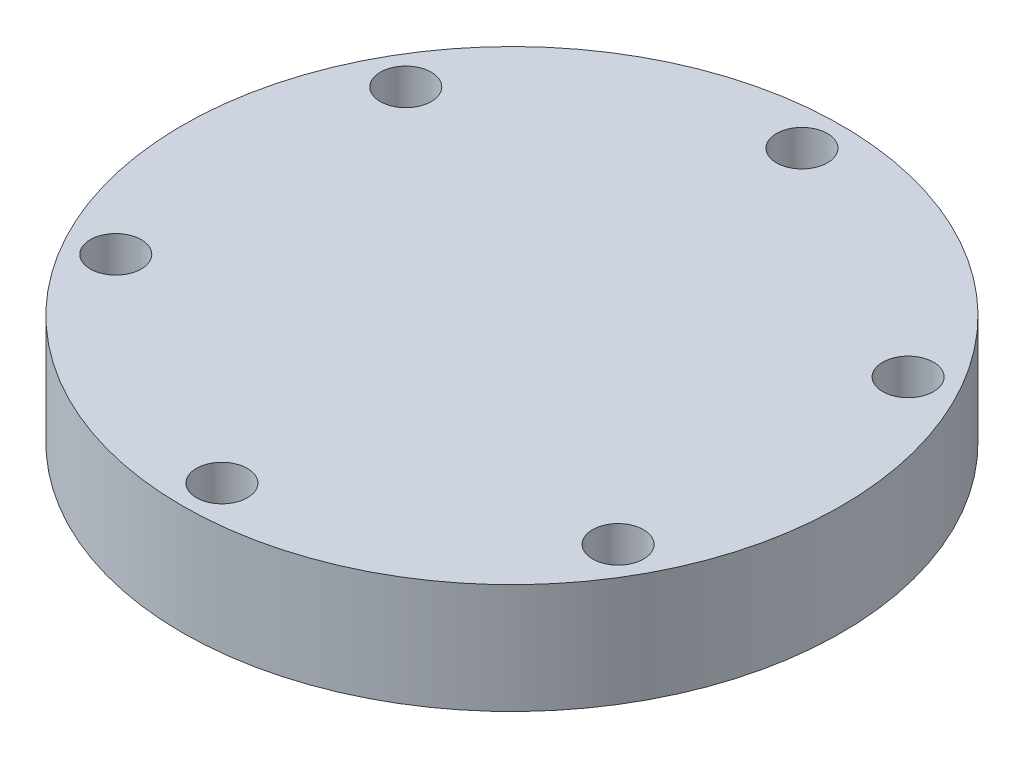
SolidWorks part; units mm, degrees
material "Copper"
ref_plane "Front Plane" through (0, 0, 0) normal (0, 0, 1) x (1, 0, 0)
ref_plane "Top Plane" through (0, 0, 0) normal (0, 1, 0) x (1, 0, 0)
ref_plane "Right Plane" through (0, 0, 0) normal (1, 0, 0) x (0, 0, -1)
ref_axis "Y Axis" through (0, 6.6675, 0) along (0, -1, 0)
sketch "outer" plane through (0, 0, 0) normal (0, 1, 0) x (1, 0, 0)
  circle A0 centre (0, 0) radius 19.05
  dimension "D1" = 38.1
extrude "Body" add sketch "outer" along normal blind 6.35
sketch "inner" plane through (0, 0, 0) normal (0, 1, 0) x (1, 0, 0)
  circle A0 centre (0, 0) radius 11.938
  dimension "D1" = 23.876
extrude "Pocket" cut sketch "inner" along normal blind 3.81
sketch "Screw Position" plane through (0, 0, 0) normal (0, 1, 0) x (1, 0, 0)
  point P0 (0, 16.764)
  dimension "D1" = 16.764
hole_wizard "#4 Clearance Hole1" positions "Sketch7" profile "Sketch8" hole size "#4" standard "ANSI Inch" end condition through all
sketch "Sketch7" plane through (0, 6.35, 0) normal (0, 1, 0) x (1, 0, 0)
  point P0 (0, 16.764)
sketch "Sketch8" plane through (0, 6.35, -16.764) normal (1, 0, 0) x (0, 0, 1)
  line L0 (0, 0) -> (0, 6.35)
  line L1 (0, 6.35) -> (1.4732, 6.35)
  line L2 (1.4732, 6.35) -> (1.4732, 0)
  line L5 (1.4732, 0) -> (0, 0)
  line L11 (0, -6.35) -> (0, 107.95) construction
  dimension "Thru Hole Dia." = 2.9464
  dimension "Thru Hole Depth" = 6.35
pattern_circular "Screw Holes" count 6 over 360 about axis through (0, 6.6675, 0) along (0, -1, 0) of "#4 Clearance Hole1"
sketch "Post Sketch" plane through (0, 0, 0) normal (0, 1, 0) x (1, 0, 0)
  circle A0 centre (0, -7) radius 1.2065
  circle A1 centre (5.3033, -5.3033) radius 1.2065
  point P0 (0, -7)
  point P1 (5.3033, -5.3033)
  dimension "D3" = 2.413
  dimension "D4" = 2.413
  dimension "D1" = 7
  dimension "D2" = 7.5
extrude "Post" add sketch "Post Sketch" against normal blind 4.572 from surface starting at face at (0, 3.81, 11.938)
pattern_circular "CirPattern1" count 4 over 360 about axis through (0, 6.6675, 0) along (0, -1, 0) of "Post"
equation "\"outer_d\"= 3 / 2in"
equation "\"top_h\"= 1 / 4in"
equation "\"screw_r\"= 0.66in"
equation "\"inner_d\"= 0.94in"
equation "\"inner_h\"= 150mil"
equation "\"D1@outer\" = \"outer_d\""
equation "\"D1@Body\" = \"top_h\""
equation "\"D1@inner\"=\"inner_d\""
equation "\"D1@Pocket\" = \"inner_h\""
equation "\"D1@Screw Position\"=\"screw_r\""
equation "\"post_r1\" = 7mm"
equation "\"post_r2\"= 7.5mm"
equation "\"post_bottom_h\" = 0.03in"
equation "\"D1@Post Sketch\" = \"post_r1\""
equation "\"D2@Post Sketch\" = \"post_r2\""
equation "\"post_d\"= 0.095in"
equation "\"D3@Post Sketch\"=\"post_d\""
equation "\"D4@Post Sketch\"=\"post_d\""
equation "\"D1@Post\" = \"inner_h\" + \"post_bottom_h\""
